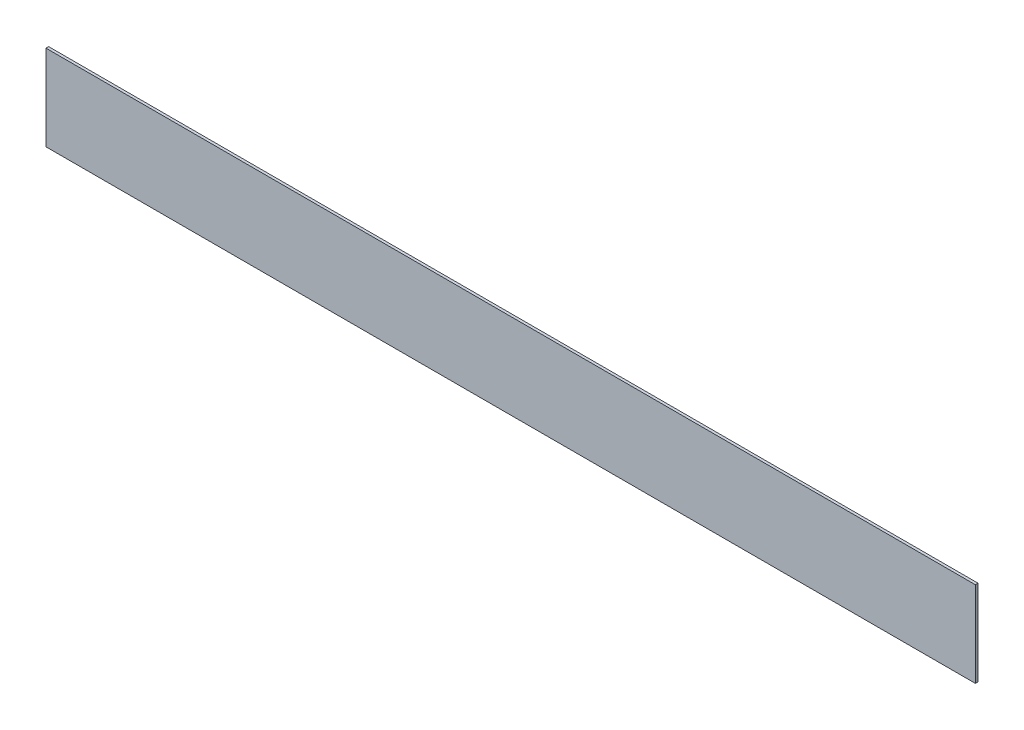
SolidWorks part; units mm, degrees
ref_plane "Front Plane" through (0, 0, 0) normal (0, 0, 1) x (1, 0, 0)
ref_plane "Top Plane" through (0, 0, 0) normal (0, 1, 0) x (1, 0, 0)
ref_plane "Right Plane" through (0, 0, 0) normal (1, 0, 0) x (0, 0, -1)
sketch "Sketch1" plane through (0, 0, 0) normal (0, 0, 1) x (1, 0, 0)
  line L1 (0, 0) -> (552.45, 0)
  line L2 (0, 0) -> (0, 50.8)
  line L3 (0, 50.8) -> (552.45, 50.8)
  line L4 (552.45, 0) -> (552.45, 50.8)
  dimension "D1" = 50.8
  dimension "D2" = 552.45
extrude "Boss-Extrude1" add sketch "Sketch1" along normal blind 1.5875
